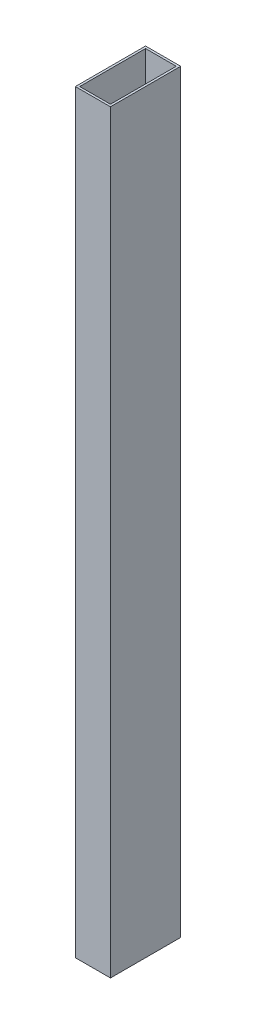
SolidWorks part; units mm, degrees
material "6061-T6 (SS)"
ref_plane "Front" through (0, 0, 0) normal (0, 0, 1) x (1, 0, 0)
ref_plane "Top" through (0, 0, 0) normal (0, 1, 0) x (1, 0, 0)
ref_plane "Right" through (0, 0, 0) normal (1, 0, 0) x (0, 0, -1)
sketch "Sketch1" plane through (0, 0, 0) normal (0, 1, 0) x (1, 0, 0)
  line L1 (12.7, 25.4) -> (-12.7, 25.4)
  line L2 (12.7, 25.4) -> (12.7, -25.4)
  line L3 (12.7, -25.4) -> (-12.7, -25.4)
  line L4 (-12.7, 25.4) -> (-12.7, -25.4)
  line L5 (12.7, 25.4) -> (-12.7, -25.4) construction
  line L6 (12.7, -25.4) -> (-12.7, 25.4) construction
  point P0 (0, 0)
  dimension "D1" = 25.4
  dimension "D2" = 50.8
extrude "Extrude-Thin1" add sketch "Sketch1" along normal up to surface (546.1 mm away) thin thin type one direction reverse wall 1.5875
